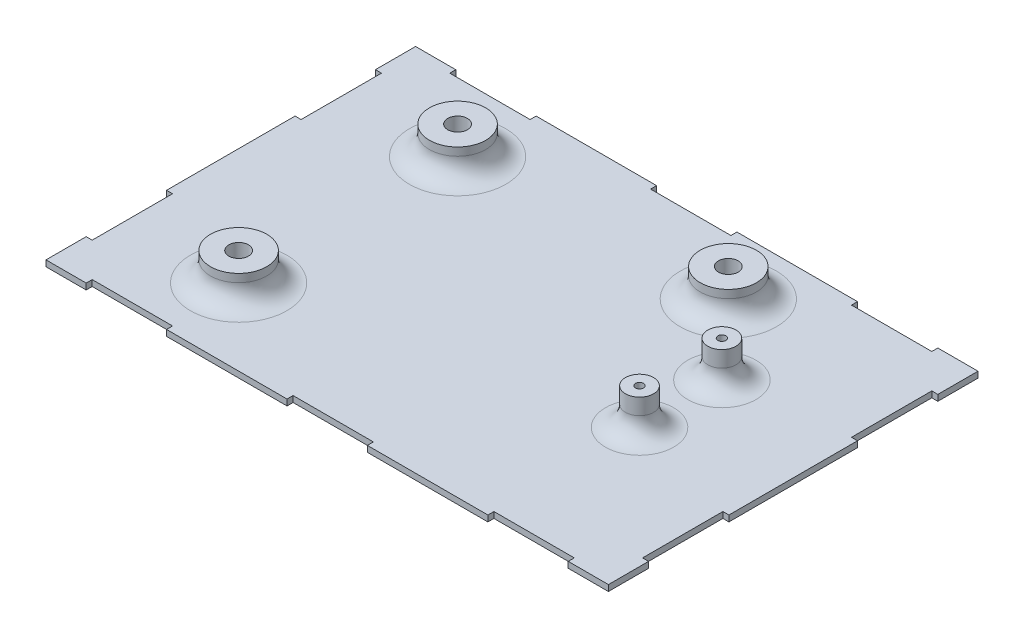
SolidWorks part; units mm, degrees
ref_plane "Front Plane" through (0, 0, 0) normal (0, 0, 1) x (1, 0, 0)
ref_plane "Top Plane" through (0, 0, 0) normal (0, 1, 0) x (1, 0, 0)
ref_plane "Right Plane" through (0, 0, 0) normal (1, 0, 0) x (0, 0, -1)
sketch "Sketch1" plane through (0, 0, 0) normal (0, 1, 0) x (1, 0, 0)
  line L1 (-70, -46) -> (70, -46)
  line L2 (-70, -46) -> (-70, 46)
  line L3 (-70, 46) -> (70, 46)
  line L4 (70, -46) -> (70, 46)
  line L5 (-70, -46) -> (70, 46) construction
  line L6 (-70, 46) -> (70, -46) construction
  point P0 (0, 0)
  dimension "D1" = 140
  dimension "D2" = 92
extrude "Boss-Extrude1" add sketch "Sketch1" along normal blind 1.5
sketch "Sketch2" plane through (0, 1.5, 0) normal (0, 1, 0) x (1, 0, 0)
  line L5 (70, -46) -> (70, 46) construction
  line L12 (70, 36) -> (68.5, 36)
  line L13 (68.5, 36) -> (68.5, 16)
  line L14 (70, 16) -> (70, 36)
  line L15 (68.5, 16) -> (70, 16)
  line L16 (70, -16) -> (68.5, -16)
  line L17 (68.5, -16) -> (68.5, -36)
  line L18 (68.5, -36) -> (70, -36)
  line L19 (70, -36) -> (70, -16)
  line L20 (70, 46) -> (-70, 46) construction
  line L21 (-70, -46) -> (70, -46) construction
  line L22 (60, -46) -> (60, -44.5)
  line L23 (60, -44.5) -> (40, -44.5)
  line L24 (40, -44.5) -> (40, -46)
  line L25 (-60, -46) -> (-60, -44.5)
  line L26 (-60, -44.5) -> (-40, -44.5)
  line L27 (-40, -44.5) -> (-40, -46)
  line L28 (-40, -46) -> (-60, -46)
  line L29 (40, -46) -> (60, -46)
  line L30 (-70, 46) -> (-70, -46) construction
  line L31 (-10, -46) -> (-10, -44.5)
  line L32 (-10, -44.5) -> (10, -44.5)
  line L33 (10, -44.5) -> (10, -46)
  line L34 (10, -46) -> (-10, -46)
  line L35 (-60, 46) -> (-60, 44.5)
  line L36 (-60, 44.5) -> (-40, 44.5)
  line L37 (-40, 44.5) -> (-40, 46)
  line L38 (-40, 46) -> (-60, 46)
  line L39 (-10, 46) -> (-10, 44.5)
  line L40 (-10, 44.5) -> (10, 44.5)
  line L41 (10, 44.5) -> (10, 46)
  line L42 (10, 46) -> (-10, 46)
  line L43 (40, 46) -> (40, 44.5)
  line L44 (40, 44.5) -> (60, 44.5)
  line L45 (60, 44.5) -> (60, 46)
  line L46 (60, 46) -> (40, 46)
  line L47 (-70, 36) -> (-68.5, 36)
  line L48 (-68.5, 36) -> (-68.5, 16)
  line L49 (-68.5, 16) -> (-70, 16)
  line L50 (-70, 16) -> (-70, 36)
  line L51 (-70, -36) -> (-68.5, -36)
  line L52 (-68.5, -36) -> (-68.5, -16)
  line L53 (-68.5, -16) -> (-70, -16)
  line L54 (-70, -16) -> (-70, -36)
  dimension "D1" = 10
  dimension "D2" = 10
  dimension "D3" = 20
  dimension "D4" = 20
  dimension "D5" = 1.5
  dimension "D6" = 1.5
  dimension "D7" = 10
  dimension "D8" = 10
  dimension "D9" = 20
  dimension "D10" = 20
  dimension "D11" = 1.5
  dimension "D12" = 1.5
  dimension "D13" = 1.5
  dimension "D14" = 20
  dimension "D15" = 30
  dimension "D16" = 1.5
  dimension "D17" = 1.5
  dimension "D18" = 1.5
  dimension "D19" = 1.5
  dimension "D20" = 1.5
  dimension "D21" = 20
  dimension "D22" = 20
  dimension "D23" = 20
  dimension "D24" = 20
  dimension "D25" = 20
extrude "Cut-Extrude1" cut sketch "Sketch2" against normal through all
sketch "Sketch3" plane through (0, 1.5, 0) normal (0, 1, 0) x (1, 0, 0)
  line L0 (-70, 46) -> (-70, 36) construction
  line L1 (-60, 44.5) -> (-40, 44.5) construction
  line L3 (70, -16) -> (70, 16) construction
  line L4 (40, 46) -> (10, 46) construction
  circle A0 centre (-41.05, 27.5) radius 7
  circle A1 centre (-41.05, -27) radius 7
  circle A2 centre (23.35, 30.5) radius 7
  circle A3 centre (40, 12.25) radius 3.5
  circle A4 centre (40, -8.25) radius 3.5
  point P16 (-39.8133, 27.4607)
  dimension "D3" = 14
  dimension "D4" = 14
  dimension "D6" = 14
  dimension "D14" = 7
  dimension "D15" = 7
  dimension "D1" = 28.95
  dimension "D2" = 17
  dimension "D5" = 54.5
  dimension "D7" = 64.4
  dimension "D8" = 0
  dimension "D9" = 3
  dimension "D10" = 30
  dimension "D11" = 30
  dimension "D12" = 33.75
  dimension "D13" = 20.5
extrude "Boss-Extrude2" add sketch "Sketch3" along normal blind 7
sketch "Sketch6" plane through (0, 8.5, 0) normal (0, 1, 0) x (1, 0, 0)
  circle A0 centre (40, 12.25) radius 3.5
  circle A1 centre (40, -8.25) radius 3.5
  dimension "D1" = 7
  dimension "D2" = 7
extrude "Boss-Extrude3" add sketch "Sketch6" along normal blind 2
sketch "Sketch7" plane through (0, 8.5, 0) normal (0, 1, 0) x (1, 0, 0)
  circle A0 centre (-41.05, 27.5) radius 2.45
  circle A2 centre (23.35, 30.5) radius 2.45
  circle A3 centre (-41.05, -27) radius 2.45
  dimension "D1" = 4.9
  dimension "D2" = 4.9
  dimension "D3" = 4.9
extrude "Cut-Extrude4" cut sketch "Sketch7" against normal blind 5.1
sketch "Sketch8" plane through (0, 10.5, 0) normal (0, 1, 0) x (1, 0, 0)
  circle A0 centre (40, 12.25) radius 1
  circle A1 centre (40, -8.25) radius 1
  dimension "D1" = 2
  dimension "D2" = 2
extrude "Cut-Extrude5" cut sketch "Sketch8" against normal blind 7
fillet "Fillet1" radius 5 5 edges at (40, 1.5, 4.75) (40, 1.5, -15.75) (23.35, 1.5, -37.5) (-41.05, 1.5, 20) (-41.05, 1.5, -34.5)
